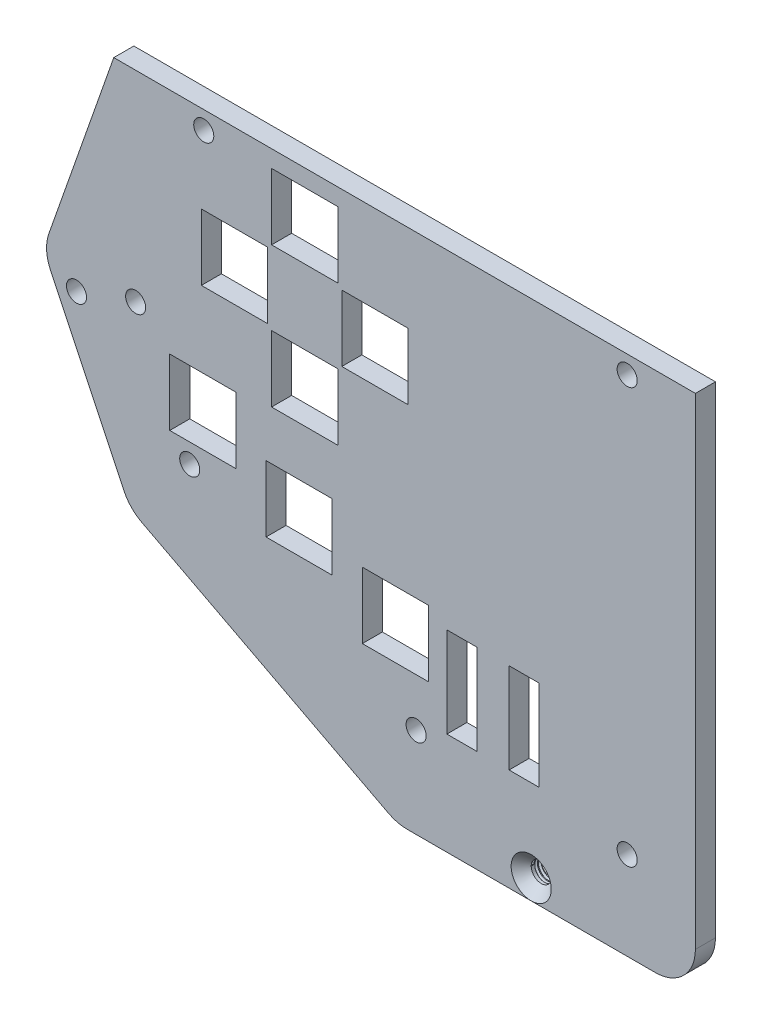
SolidWorks part; units mm, degrees
ref_plane "Front Plane" through (0, 0, 0) normal (0, 0, 1) x (1, 0, 0)
ref_plane "Top Plane" through (0, 0, 0) normal (0, 1, 0) x (1, 0, 0)
ref_plane "Right Plane" through (0, 0, 0) normal (1, 0, 0) x (0, 0, -1)
sketch "Sketch1" plane through (0, 0, 0) normal (0, 0, 1) x (1, 0, 0)
  line L6 (-20.066, -57.15) -> (46.99, -57.15) construction
  line L7 (-12.446, -73.152) -> (46.99, -73.152) construction
  line L8 (-3.3141, 6.35) -> (48.26, 6.35)
  line L9 (53.34, 1.27) -> (53.34, -92.71)
  line L10 (48.26, -97.79) -> (16.847, -97.79)
  line L16 (-8.1072, 2.9529) -> (-28.5162, -55.1739)
  line L18 (-20.066, -57.15) -> (-29.21, -57.15) construction
  line L26 (0, 0) -> (46.99, 0) construction
  line L27 (46.99, 0) -> (46.99, -88.9) construction
  line L28 (46.99, -88.9) -> (17.78, -88.9) construction
  line L29 (17.78, -88.9) -> (-12.446, -73.152) construction
  line L30 (-12.446, -73.152) -> (-20.066, -57.15) construction
  line L31 (-20.066, -57.15) -> (0, 0) construction
  line L32 (46.99, -57.15) -> (46.99, -88.9) construction
  line L33 (17.78, -88.9) -> (15.603, -97.79) construction
  line L34 (-12.446, -73.152) -> (-17.9301, -78.4424) construction
  line L35 (14.4997, -97.2152) -> (-16.7505, -80.9336)
  line L36 (-28.3096, -59.0409) -> (-18.9898, -78.6124)
  arc A0 (53.34, -92.71) -> (48.26, -97.79) centre (48.26, -92.71) cw
  arc A1 (14.4997, -97.2152) -> (16.847, -97.79) centre (16.847, -92.71) ccw
  arc A2 (-16.7505, -80.9336) -> (-18.9898, -78.6124) centre (-14.4033, -76.4284) cw
  arc A3 (-28.5162, -55.1739) -> (-28.3096, -59.0409) centre (-23.723, -56.8568) ccw
  arc A4 (-8.1072, 2.9529) -> (-3.3141, 6.35) centre (-3.3141, 1.27) cw
  arc A5 (48.26, 6.35) -> (53.34, 1.27) centre (48.26, 1.27) cw
  point P13 (53.34, -97.79)
  point P32 (53.34, 6.35)
  dimension "D8" = 5.08
  dimension "D1" = 88.9
  dimension "D2" = 29.21
  dimension "D3" = 59.436
  dimension "D4" = 67.056
  dimension "D5" = 104.14
  dimension "D6" = 82.55
  dimension "D7" = 46.99
  dimension "D13" = 103.76
  dimension "D17" = 108.51
sketch "Sketch3" plane through (0, 0, 0) normal (0, 0, 1) x (1, 0, 0)
  line L6 (-20.066, -57.15) -> (46.99, -57.15) construction
  line L7 (-12.446, -73.152) -> (46.99, -73.152) construction
  line L8 (0, 0) -> (46.99, 0) construction
  line L9 (46.99, 0) -> (46.99, -88.9) construction
  line L10 (46.99, -88.9) -> (17.78, -88.9) construction
  line L11 (17.78, -88.9) -> (-12.446, -73.152) construction
  line L12 (-12.446, -73.152) -> (-20.066, -57.15) construction
  line L13 (-20.066, -57.15) -> (0, 0) construction
  line L14 (3.8784, -55.88) -> (3.8784, -38.1) construction
  circle A0 centre (3.8784, -38.1) radius 5.08
  circle A1 centre (-5.0116, -46.99) radius 5.08
  circle A2 centre (3.8784, -55.88) radius 5.08
  circle A3 centre (12.7684, -46.99) radius 5.08
  circle A4 centre (-9.144, -65.024) radius 5.08
  circle A5 centre (3.048, -70.612) radius 5.08
  circle A6 centre (15.24, -76.2) radius 5.08
  dimension "D7" = 10.16
  dimension "D1" = 43.1116
  dimension "D2" = 8.89
  dimension "D3" = 8.89
  dimension "D4" = 46.99
  dimension "D5" = 8.89
  dimension "D6" = 8.89
  dimension "D8" = 12.192
  dimension "D9" = 5.588
  dimension "D10" = 5.588
  dimension "D11" = 12.192
  dimension "D12" = 43.942
  dimension "D13" = 70.612
sketch "Sketch10" plane through (0, 0, 0) normal (0, 0, 1) x (1, 0, 0)
  line L1 (53.34, -31.75) -> (53.34, -92.71)
  line L6 (48.26, -97.79) -> (16.847, -97.79)
  line L16 (-20.2918, -31.75) -> (-28.5162, -55.1739)
  line L19 (53.34, 1.27) -> (53.34, -92.71) construction
  line L20 (53.34, -31.75) -> (-20.2918, -31.75)
  line L21 (-8.1072, 2.9529) -> (-28.5162, -55.1739) construction
  line L24 (14.4997, -97.2152) -> (-16.7505, -80.9336)
  line L25 (-18.9898, -78.6124) -> (-28.3096, -59.0409)
  arc A0 (-18.9898, -78.6124) -> (-16.7505, -80.9336) centre (-14.4033, -76.4284) ccw
  arc A1 (16.847, -97.79) -> (14.4997, -97.2152) centre (16.847, -92.71) cw
  arc A2 (-28.5162, -55.1739) -> (-28.3096, -59.0409) centre (-23.723, -56.8568) ccw
  arc A3 (53.34, -92.71) -> (48.26, -97.79) centre (48.26, -92.71) cw
  point P13 (15.603, -97.79)
  point P17 (-29.21, -57.15)
  point P20 (53.34, -97.79)
  dimension "D1" = 5.08
extrude "Boss-Extrude1" add sketch "Sketch10" along normal blind 2.54
sketch "Sketch11" plane through (0, 0, 2.54) normal (0, 0, 1) x (1, 0, 0)
  line L0 (46.99, -88.9) -> (17.78, -88.9) construction
  line L5 (33.561, -73.406) -> (29.751, -73.406)
  line L6 (33.561, -73.406) -> (33.561, -84.836)
  line L11 (33.561, -84.836) -> (29.751, -84.836)
  line L12 (29.751, -73.406) -> (29.751, -84.836)
  line L18 (46.99, 0) -> (46.99, -88.9) construction
  line L23 (25.687, -73.406) -> (21.877, -73.406)
  line L24 (25.687, -73.406) -> (25.687, -84.836)
  line L29 (25.687, -84.836) -> (21.877, -84.836)
  line L30 (21.877, -73.406) -> (21.877, -84.836)
  line L42 (8.0694, -51.689) -> (-0.3126, -51.689)
  line L43 (8.0694, -51.689) -> (8.0694, -60.071)
  line L44 (8.0694, -60.071) -> (-0.3126, -60.071)
  line L45 (-0.3126, -51.689) -> (-0.3126, -60.071)
  line L46 (-0.8206, -42.799) -> (-9.2026, -42.799)
  line L47 (-0.8206, -42.799) -> (-0.8206, -51.181)
  line L48 (-0.8206, -51.181) -> (-9.2026, -51.181)
  line L49 (-9.2026, -42.799) -> (-9.2026, -51.181)
  line L52 (8.0694, -42.291) -> (-0.3126, -42.291)
  line L53 (-0.3126, -33.909) -> (-0.3126, -42.291)
  line L54 (16.9594, -42.799) -> (8.5774, -42.799)
  line L55 (16.9594, -42.799) -> (16.9594, -51.181)
  line L56 (16.9594, -51.181) -> (8.5774, -51.181)
  line L57 (8.5774, -42.799) -> (8.5774, -51.181)
  line L58 (-0.3126, -33.909) -> (8.0694, -33.909)
  line L59 (8.0694, -33.909) -> (8.0694, -42.291)
  line L60 (3.8784, -51.689) -> (3.8784, -60.071) construction
  line L61 (-0.3126, -55.88) -> (8.0694, -55.88) construction
  line L62 (-5.0116, -51.181) -> (-5.0116, -42.799) construction
  line L63 (-9.2026, -46.99) -> (-0.8206, -46.99) construction
  line L64 (12.7684, -42.799) -> (12.7684, -51.181) construction
  line L65 (8.5774, -46.99) -> (16.9594, -46.99) construction
  line L66 (3.8784, -33.909) -> (3.8784, -42.291) construction
  line L67 (-0.3126, -38.1) -> (8.0694, -38.1) construction
  line L68 (-4.826, -60.706) -> (-4.826, -69.088)
  line L69 (-13.208, -65.024) -> (-5.08, -65.024) construction
  line L70 (-9.144, -60.96) -> (-9.144, -69.088) construction
  line L71 (-4.826, -69.088) -> (-13.208, -69.088)
  line L72 (-13.208, -60.706) -> (-13.208, -69.088)
  line L73 (-4.826, -60.706) -> (-13.208, -60.706)
  line L74 (7.366, -66.294) -> (7.366, -74.676)
  line L75 (-1.016, -70.612) -> (7.112, -70.612) construction
  line L76 (3.048, -66.548) -> (3.048, -74.676) construction
  line L77 (7.366, -74.676) -> (-1.016, -74.676)
  line L78 (-1.016, -66.294) -> (-1.016, -74.676)
  line L79 (7.366, -66.294) -> (-1.016, -66.294)
  line L80 (19.558, -71.882) -> (19.558, -80.264)
  line L81 (11.176, -76.2) -> (19.304, -76.2) construction
  line L82 (15.24, -72.136) -> (15.24, -80.264) construction
  line L83 (19.558, -80.264) -> (11.176, -80.264)
  line L84 (11.176, -71.882) -> (11.176, -80.264)
  line L85 (19.558, -71.882) -> (11.176, -71.882)
  dimension "D1" = 4.064
  dimension "D3" = 13.429
  dimension "D4" = 11.43
  dimension "D5" = 3.81
  dimension "D6" = 4.064
  dimension "D7" = 11.43
  dimension "D8" = 4.064
  dimension "D13" = 3.81
  dimension "D21" = 8.382
  dimension "D22" = 8.382
extrude "Cut-Extrude1" cut sketch "Sketch11" against normal through all both and the other way through all
sketch "Sketch12" plane through (0, 0, 0) normal (0, 0, -1) x (-1, 0, 0)
  line L0 (20.066, -57.15) -> (-46.99, -57.15) construction
  line L1 (-53.34, -31.75) -> (20.2918, -31.75) construction
  line L2 (-46.99, 0) -> (-46.99, -88.9) construction
  line L3 (8.9024, -34.036) -> (11.9504, -34.036) construction
  line L4 (20.066, -57.15) -> (0, 0) construction
  line L5 (17.526, -57.15) -> (20.066, -57.15) construction
  line L6 (12.446, -73.152) -> (20.066, -57.15) construction
  line L7 (10.6765, -71.5339) -> (13.2165, -71.5339) construction
  line L8 (10.6765, -71.5339) -> (10.6765, -74.0739) construction
  line L9 (-17.78, -88.9) -> (12.446, -73.152) construction
  line L10 (-46.99, -88.9) -> (-17.78, -88.9) construction
  line L11 (-17.9848, -86.36) -> (-12.9048, -86.36) construction
  circle A0 centre (-44.704, -34.036) radius 1.27
  circle A1 centre (8.9024, -34.036) radius 1.27
  circle A2 centre (17.526, -57.15) radius 1.27
  circle A3 centre (-44.704, -86.614) radius 1.27
  circle A4 centre (-17.9848, -86.36) radius 1.27
  circle A5 centre (10.6765, -71.5339) radius 1.27
  dimension "D1" = 2.54
  dimension "D6" = 2.54
  dimension "D7" = 2.54
  dimension "D2" = 2.286
  dimension "D3" = 2.286
  dimension "D4" = 2.286
  dimension "D5" = 3.048
  dimension "D8" = 2.54
  dimension "D9" = 2.54
  dimension "D10" = 5.08
  dimension "D11" = 2.286
  dimension "D12" = 2.286
extrude "Cut-Extrude2" cut sketch "Sketch12" against normal through all both and the other way through all
sketch "Sketch13" plane through (0, 0, 0) normal (0, 0, -1) x (-1, 0, 0)
  line L0 (28.3096, -59.0409) -> (18.9898, -78.6124) construction
  line L1 (8.1072, 2.9529) -> (28.5162, -55.1739) construction
  line L3 (-48.26, -97.79) -> (-16.847, -97.79) construction
  circle A1 centre (25.0123, -59.762) radius 1.27
  circle A3 centre (-32.5535, -95.25) radius 1.27
  point P10 (-32.5535, -95.25)
  dimension "D1" = 2.54
  dimension "D2" = 4.826
  dimension "D4" = 2.54
  dimension "D3" = 2.667
extrude "Cut-Extrude3" cut sketch "Sketch13" against normal through all both and the other way through all
chamfer "Chamfer1" distance 1.27 angle 45 1 edges at (31.2835, -95.25, 2.54)
thread "Thread1" pitch 0.4536 method cut profile "Thread Profile1" start angle 0, offset 0, length 6.35, pitch 0.4536, diameter 2.54
ref_plane "Plane1" through (31.2835, -95.25, 1.27) normal (0, -1, 0) x (-1, 0, 0)
sketch "Thread Profile1" plane through (31.2835, -95.25, 1.27) normal (0, -1, 0) x (-1, 0, 0)
  line L0 (0, 0) -> (0, 0.4536) construction
  line L1 (0, 0) -> (0.2455, 0.1417)
  line L2 (0.2455, 0.1417) -> (0.2455, 0.1984)
  line L3 (0.2455, 0.1984) -> (0, 0.3402)
  line L4 (0.2455, 0.1701) -> (0, 0.1701) construction
  line L11 (0, 0) -> (0, 0.3402)
  point P2 (0, 0)
  dimension "Pitch" = 0.4536
  dimension "Profile_Angle" = 60
  dimension "Profile_Land" = 0.0567
  dimension "Profile_Height" = 0.2455
